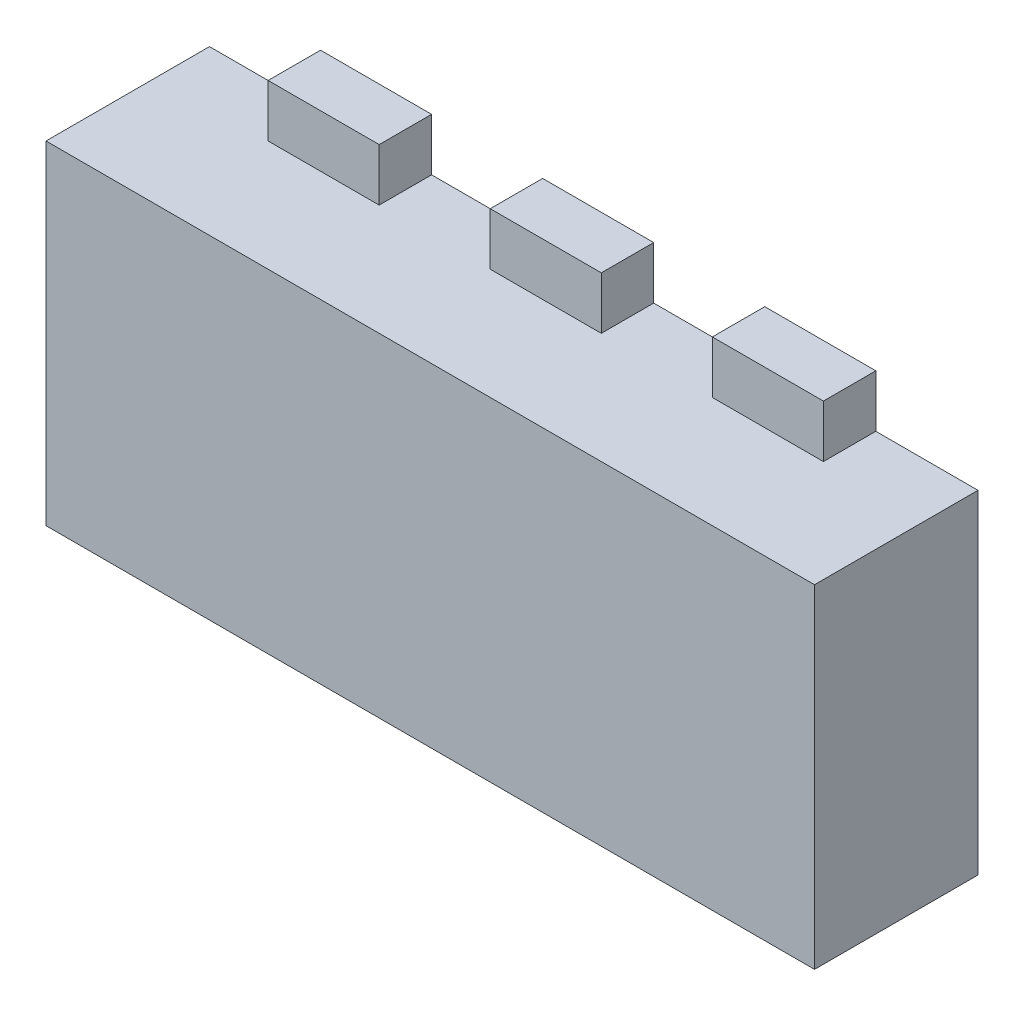
SolidWorks part; units mm, degrees
ref_plane "Front Plane" through (0, 0, 0) normal (0, 0, 1) x (1, 0, 0)
ref_plane "Top Plane" through (0, 0, 0) normal (0, 1, 0) x (1, 0, 0)
ref_plane "Right Plane" through (0, 0, 0) normal (1, 0, 0) x (0, 0, -1)
sketch "Sketch1" plane through (0, 0, 0) normal (0, 0, 1) x (1, 0, 0)
  line L1 (-21.971, -9.525) -> (21.971, -9.525)
  line L2 (-21.971, -9.525) -> (-21.971, 9.525)
  line L3 (-21.971, 9.525) -> (21.971, 9.525)
  line L4 (21.971, -9.525) -> (21.971, 9.525)
  line L5 (-21.971, -9.525) -> (21.971, 9.525) construction
  line L6 (-21.971, 9.525) -> (21.971, -9.525) construction
  point P0 (0, 0)
  dimension "D1" = 19.05
  dimension "D2" = 43.942
extrude "Body" add sketch "Sketch1" along normal blind 2.9972
sketch "Sketch2" plane through (0, 9.525, 0) normal (0, 1, 0) x (1, 0, 0)
  line L0 (21.971, 0) -> (-21.971, 0) construction
  line L1 (-15.621, 0) -> (-9.271, 0)
  line L2 (-15.621, 0) -> (-15.621, -2.9972)
  line L3 (-15.621, -2.9972) -> (-9.271, -2.9972)
  line L4 (-9.271, 0) -> (-9.271, -2.9972)
  line L5 (21.971, -2.9972) -> (-21.971, -2.9972) construction
  line L6 (-21.971, -2.9972) -> (-21.971, 0) construction
  dimension "D1" = 6.35
  dimension "D2" = 6.35
extrude "Tab" add sketch "Sketch2" along normal blind 2.9972
sketch "Sketch3" plane through (0, 0, 2.9972) normal (0, 0, 1) x (1, 0, 0)
  line L0 (-14.859, 12.5222) -> (-14.859, 8.255)
  line L1 (-15.621, 12.5222) -> (-9.271, 12.5222) construction
  line L2 (-14.859, 8.255) -> (-14.224, 8.255)
  line L3 (-14.224, 8.255) -> (-14.224, 12.5222)
  line L4 (-15.621, 9.525) -> (-9.271, 9.525) construction
  line L5 (-12.446, 9.525) -> (-12.446, 12.5222) construction
  line L6 (-14.859, 12.5222) -> (-14.224, 12.5222)
  line L7 (-10.033, 12.5222) -> (-10.668, 12.5222)
  line L8 (-10.668, 8.255) -> (-10.668, 12.5222)
  line L9 (-10.033, 8.255) -> (-10.668, 8.255)
  line L10 (-10.033, 12.5222) -> (-10.033, 8.255)
  line L11 (-8.636, 9.525) -> (-8.636, 8.255)
  line L12 (-15.621, 9.525) -> (-16.256, 9.525)
  line L13 (-15.621, 9.525) -> (-15.621, 8.255)
  line L14 (-15.621, 8.255) -> (-16.256, 8.255)
  line L15 (-16.256, 9.525) -> (-16.256, 8.255)
  line L16 (-9.271, 8.255) -> (-8.636, 8.255)
  line L17 (-9.271, 9.525) -> (-9.271, 8.255)
  line L18 (-9.271, 9.525) -> (-8.636, 9.525)
  line L19 (-15.621, 12.5222) -> (-15.621, 9.525) construction
  dimension "D1" = 0.635
  dimension "D2" = 0.635
  dimension "D3" = 1.27
  dimension "D4" = 0.762
extrude "Slots" [suppressed] cut sketch "Sketch3" against normal through all
fillet "Fillet1" [suppressed] radius 0.254
ref_plane "Tab Midplane" [suppressed] through (-12.7, 0, 0) normal (-1, 0, 0) x (0, 0, 1)
ref_plane "Body Horizontal Midplane" through (0, 0, 0) normal (0, 1, 0) x (1, 0, 0)
ref_plane "Body Vertical Midplane" through (0, 0, 0) normal (-1, 0, 0) x (0, 0, 1)
pattern_linear "LPattern1" count 3 spacing 12.7 along (1, 0, 0) of "Tab"
mirror "Mirror1" about plane through (0, 0, 0) normal (0, 1, 0) of "LPattern1"
sketch "Sketch5" plane through (0, 0, 2.9972) normal (0, 0, 1) x (1, 0, 0)
  line L1 (-21.971, 9.525) -> (21.971, 9.525)
  line L2 (-21.971, 9.525) -> (-21.971, -9.525)
  line L3 (-21.971, -9.525) -> (21.971, -9.525)
  line L4 (21.971, 9.525) -> (21.971, -9.525)
extrude "Boss-Extrude1" add sketch "Sketch5" along normal blind 6.35
